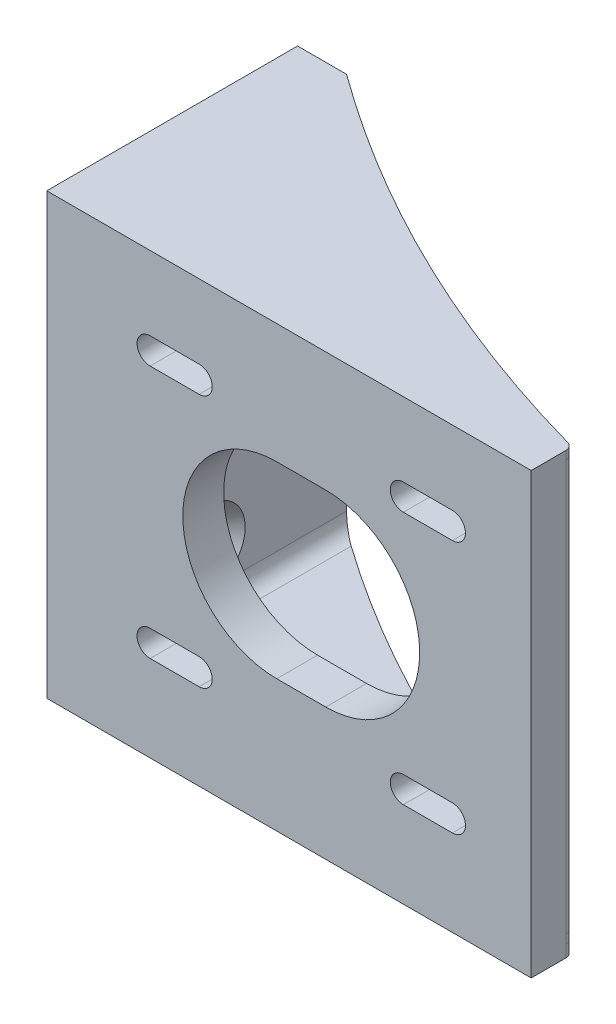
SolidWorks part; units mm, degrees
note: The reader was unsure of these and kept them because the rebuilt part matched: shared geometry of "Croquis1<3>", "Croquis3<2>".
ref_plane "Front Plane" through (0, 0, 0) normal (0, 0, 1) x (1, 0, 0)
ref_plane "Top Plane" through (0, 0, 0) normal (0, 1, 0) x (1, 0, 0)
ref_plane "Right Plane" through (0, 0, 0) normal (1, 0, 0) x (0, 0, -1)
sketch "Croquis1" plane through (0, 0, 0) normal (0, 0, 1) x (1, 0, 0)
  line L0 (-674.4454, 18.3635) -> (-668.4454, 18.3635) construction
  line L1 (-674.4454, 19.9635) -> (-668.4454, 19.9635)
  line L2 (-674.4454, 16.7635) -> (-668.4454, 16.7635)
  line L3 (-705.4454, 18.3635) -> (-699.4454, 18.3635) construction
  line L4 (-705.4454, 19.9635) -> (-699.4454, 19.9635)
  line L5 (-705.4454, 16.7635) -> (-699.4454, 16.7635)
  line L6 (-705.4454, 49.3635) -> (-699.4454, 49.3635) construction
  line L7 (-705.4454, 50.9635) -> (-699.4454, 50.9635)
  line L8 (-705.4454, 47.7635) -> (-699.4454, 47.7635)
  line L9 (-674.4454, 49.3635) -> (-668.4454, 49.3635) construction
  line L10 (-674.4454, 50.9635) -> (-668.4454, 50.9635)
  line L11 (-674.4454, 47.7635) -> (-668.4454, 47.7635)
  line L12 (-689.9454, 33.8635) -> (-683.9454, 33.8635) construction
  line L13 (-689.9454, 45.3635) -> (-683.9454, 45.3635)
  line L14 (-689.9454, 22.3635) -> (-683.9454, 22.3635)
  line L48 (-707.5096, 56.0135) -> (-712.0954, 51.4277)
  line L49 (-712.0954, 16.2993) -> (-707.5096, 11.7135)
  line L50 (-667.7954, 51.4277) -> (-672.3812, 56.0135)
  line L51 (-672.3812, 11.7135) -> (-667.7954, 16.2993)
  line L52 (-712.0954, 51.4277) -> (-712.0954, 16.2993)
  line L53 (-672.3812, 56.0135) -> (-707.5096, 56.0135)
  line L54 (-667.7954, 16.2993) -> (-667.7954, 51.4277)
  line L55 (-707.5096, 11.7135) -> (-672.3812, 11.7135)
  line L60 (-712.0954, 56.0135) -> (-712.0954, 11.7135)
  line L61 (-672.3812, 56.0135) -> (-712.0954, 56.0135)
  line L62 (-667.7954, 16.2993) -> (-667.7954, 51.4277) construction
  line L63 (-712.0954, 11.7135) -> (-672.3812, 11.7135)
  line L64 (-672.3812, 11.7135) -> (-661.7954, 11.7135)
  line L65 (-661.7954, 11.7135) -> (-661.7954, 56.0135)
  line L66 (-661.7954, 56.0135) -> (-672.3812, 56.0135)
  line L67 (-672.3812, 59.0135) -> (-715.0954, 59.0135)
  line L68 (-715.0954, 59.0135) -> (-715.0954, 8.7135) construction
  line L69 (-715.0954, 8.7135) -> (-672.3812, 8.7135)
  line L70 (-672.3812, 8.7135) -> (-658.7954, 8.7135)
  line L71 (-658.7954, 8.7135) -> (-658.7954, 59.0135)
  line L72 (-658.7954, 59.0135) -> (-672.3812, 59.0135)
  line L73 (-715.0954, 8.7135) -> (-716.0954, 8.7135)
  line L74 (-716.0954, 8.7135) -> (-716.0954, 59.0135)
  line L75 (-716.0954, 59.0135) -> (-715.0954, 59.0135)
  circle A4 centre (-689.9454, 33.8635) radius 11.5 construction
  circle A5 centre (-689.9454, 33.8635) radius 11.5 construction
  arc A6 (-674.4454, 19.9635) -> (-674.4454, 16.7635) centre (-674.4454, 18.3635) ccw
  arc A7 (-668.4454, 16.7635) -> (-668.4454, 19.9635) centre (-668.4454, 18.3635) ccw
  arc A8 (-705.4454, 19.9635) -> (-705.4454, 16.7635) centre (-705.4454, 18.3635) ccw
  arc A9 (-699.4454, 16.7635) -> (-699.4454, 19.9635) centre (-699.4454, 18.3635) ccw
  arc A10 (-705.4454, 50.9635) -> (-705.4454, 47.7635) centre (-705.4454, 49.3635) ccw
  arc A11 (-699.4454, 47.7635) -> (-699.4454, 50.9635) centre (-699.4454, 49.3635) ccw
  arc A12 (-674.4454, 50.9635) -> (-674.4454, 47.7635) centre (-674.4454, 49.3635) ccw
  arc A13 (-668.4454, 47.7635) -> (-668.4454, 50.9635) centre (-668.4454, 49.3635) ccw
  arc A14 (-689.9454, 45.3635) -> (-689.9454, 22.3635) centre (-689.9454, 33.8635) ccw
  arc A15 (-683.9454, 22.3635) -> (-683.9454, 45.3635) centre (-683.9454, 33.8635) ccw
  point P14 (-671.4454, 18.3635)
  point P19 (-702.4454, 18.3635)
  point P31 (-702.4454, 49.3635)
  point P38 (-671.4454, 49.3635)
  point P45 (-686.9454, 33.8635)
  dimension "D4" = 6
  dimension "D6" = 1.6
  dimension "D8" = 11.5
  dimension "D2" = 6
  dimension "D5" = 1
  dimension "D7" = 6
  dimension "D1" = 1
  dimension "D3" = 3
extrude "Saliente-Extruir1" add sketch "Croquis1" along normal blind 5 contours L75 L74 L73 L69 L70 L71 L72 L67 L66 L65 L64 L63 L60 L61 | L65 L66 L61 L60 L63 L64 A13 L11 A12 L10 A11 L8 A10 L7 A9 L5 A8 L4 A7 L2 A6 L1 A5
extrude "Saliente-Extruir2" add sketch "Croquis1<3>" against normal up to surface (25.7 mm away) contours L75 L74 L73 L69 L70 L71 L72 L67 L66 L65 L64 L63 L60 L61
sketch "Croquis1<3>" plane through (0, 0, 0) normal (0, 0, 1) x (1, 0, 0) same geometry as "Croquis1"
sketch "Croquis2" plane through (0, 8.7135, 0) normal (0, -1, 0) x (1, 0, 0)
  line L8 (-712.0954, 0) -> (-661.7954, 0) construction
  line L9 (-712.0954, 0) -> (-658.7954, 0)
  line L10 (-658.7954, 5) -> (-658.7954, -25.7) construction
  line L11 (-712.0954, -25.7) -> (-712.0954, 0) construction
  line L12 (-712.0954, -25.7) -> (-712.0954, 0)
  spline S0 degree 2 poles (-712.0954, -25.7) (-687.8854, -8.0483) (-658.7954, 0) knots 0 0 0 1 1 1
extrude "Cortar-Extruir2" cut sketch "Croquis2" against normal blind 80
sketch "Croquis3" plane through (0, 8.7135, 0) normal (0, -1, 0) x (1, 0, 0)
  line L4 (-658.7954, 0) -> (-658.7954, 5)
  line L5 (-658.7954, 5) -> (-716.0954, 5)
  line L6 (-716.0954, 5) -> (-716.0954, -25.7)
  line L7 (-716.0954, -25.7) -> (-712.0954, -25.7)
  line L8 (-658.7954, 0) -> (-658.7954, 5)
  line L9 (-658.7954, 5) -> (-716.0954, 5)
  line L10 (-716.0954, 5) -> (-716.0954, -25.7)
  line L11 (-716.0954, -25.7) -> (-712.0954, -25.7)
  parabola Q1 (-712.0954, -25.7) -> (-658.7954, 0) focus (-652.9065, -84.3645) apex (-689.7022, -11.9527)
  parabola Q2 (-712.0954, -25.7) -> (-658.7954, 0) focus (-652.9065, -84.3645) apex (-689.7022, -11.9527)
  dimension "D1" = 0
extrude "Saliente-Extruir3" add sketch "Croquis3" along normal blind 1
extrude "Saliente-Extruir4" add sketch "Croquis3<2>" against normal blind 1 from surface at -50.3 starting at face at (-687.0454, 59.0135, -5.71)
sketch "Croquis3<2>" plane through (0, 8.7135, 0) normal (0, -1, 0) x (1, 0, 0) same geometry as "Croquis3"
sketch "Croquis4" plane through (-716.0954, 0, 0) normal (-1, 0, 0) x (0, 0, 1)
  line L4 (5, 7.7135) -> (5, 60.0135)
  line L5 (5, 60.0135) -> (-25.7, 60.0135)
  line L6 (-25.7, 60.0135) -> (-25.7, 7.7135)
  line L7 (-25.7, 7.7135) -> (5, 7.7135)
  line L8 (5, 7.7135) -> (5, 60.0135)
  line L9 (5, 60.0135) -> (-25.7, 60.0135)
  line L10 (-25.7, 60.0135) -> (-25.7, 7.7135)
  line L11 (-25.7, 7.7135) -> (5, 7.7135)
  dimension "D1" = 0
extrude "Saliente-Extruir5" add sketch "Croquis4" along normal blind 2
sketch "Croquis6" plane through (-712.0954, 0, 0) normal (1, 0, 0) x (0, 0, -1)
  line L0 (25.7, 7.7135) -> (-5, 7.7135) construction
  line L1 (25.7, 7.7135) -> (-5, 7.7135)
  line L2 (12.2, 7.7135) -> (12.2, 63.0833) construction
  line L3 (25.7, 60.0135) -> (25.7, 7.7135) construction
  line L4 (25.7, 60.0135) -> (25.7, 7.7135) construction
  line L5 (-5, 60.0135) -> (25.7, 60.0135) construction
  circle A0 centre (19.2, 48.0135) radius 2.15
  circle A1 centre (8.7, 18.2135) radius 2.15
  circle A2 centre (5.2, 48.0135) radius 2.15
  dimension "D3" = 4.3
  dimension "D1" = 12
  dimension "D2" = 7
  dimension "D4" = 10.5
  dimension "D5" = 13.5
  dimension "D6" = 17
hole_wizard "Avellanado para tornillo con cabeza avellanada de clavija hexagonal de M41" positions "Croquis7" profile "Croquis8" countersink size "M4" standard "DIN"
sketch "Croquis7" plane through (-712.0954, 0, 0) normal (1, 0, 0) x (0, 0, -1)
  point P0 (19.2, 48.0135)
  point P3 (5.2, 48.0135)
  point P6 (8.7, 18.2135)
sketch "Croquis8" plane through (-712.0954, 48.0135, -19.2) normal (0, 1, 0) x (0, 0, -1)
  line L0 (0, 0) -> (0, 6)
  line L1 (0, 6) -> (2.25, 6)
  line L2 (2.25, 6) -> (2.25, 2.34)
  line L3 (2.25, 2.34) -> (4.59, 0)
  line L5 (4.59, 0) -> (0, 0)
  line L6 (-2.25, 2.34) -> (-4.59, 0) construction
  line L11 (0, -6.35) -> (0, 107.95) construction
  dimension "Diámetro de taladro hasta el siguiente" = 4.5
  dimension "Profundidad de taladro hasta el siguiente" = 6
  dimension "Diámetro de avellanado cercano" = 9.18
  dimension "Ángulo de avellanado cercano" = 90
sketch "Croquis11" plane through (0, 7.7135, 0) normal (0, -1, 0) x (1, 0, 0)
  line L4 (-658.7954, 5) -> (-718.0954, 5)
  line L5 (-718.0954, 5) -> (-718.0954, -25.7)
  line L6 (-718.0954, -25.7) -> (-712.0954, -25.7)
  line L7 (-658.7954, 0) -> (-658.7954, 5)
  line L8 (-658.7954, 5) -> (-718.0954, 5)
  line L9 (-718.0954, 5) -> (-718.0954, -25.7)
  line L10 (-718.0954, -25.7) -> (-712.0954, -25.7)
  line L11 (-658.7954, 0) -> (-658.7954, 5)
  parabola Q1 (-712.0954, -25.7) -> (-658.7954, 0) focus (-652.9065, -84.3645) apex (-689.7022, -11.9527)
  parabola Q2 (-712.0954, -25.7) -> (-658.7954, 0) focus (-652.9065, -84.3645) apex (-689.7022, -11.9527)
  dimension "D1" = 0
extrude "Saliente-Extruir7" add sketch "Croquis11" along normal blind 1.5
fillet "Redondeo1" radius 1 4 edges at (-658.7954, 59.5135, 0) (-658.7954, 6.9635, 0) (-658.7954, 8.2135, 0) (-658.7954, 33.8635, 0)
fillet "Redondeo5" radius 2 1 edges at (-712.0954, 11.7135, -12.85)
fillet "Redondeo6" radius 2 1 edges at (-712.0954, 56.0135, -12.85)
